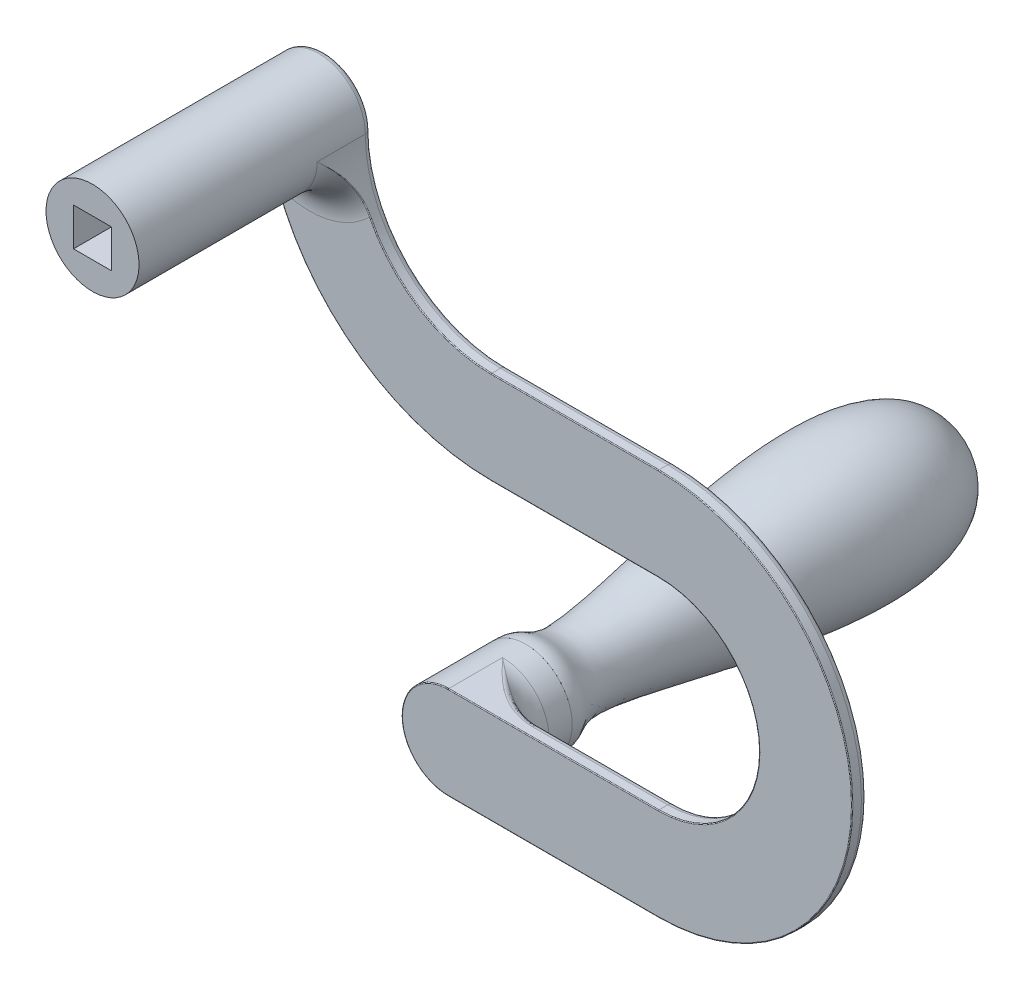
SolidWorks part; units mm, degrees
ref_plane "Front" through (0, 0, 0) normal (0, 0, 1) x (1, 0, 0)
ref_plane "Top" through (0, 0, 0) normal (0, 1, 0) x (1, 0, 0)
ref_plane "Right" through (0, 0, 0) normal (1, 0, 0) x (0, 0, -1)
sketch "Sketch1" plane through (0, 0, 0) normal (0, 0, 1) x (1, 0, 0)
  line L0 (-21.5754, 25) -> (0, 25)
  line L1 (-27.1185, -25) -> (0, -25)
  line L2 (-21.5754, 13) -> (0, 13)
  line L3 (-27.1185, -13) -> (0, -13)
  line L4 (-51.0187, 42.4433) -> (-39.0187, 42.4433)
  line L5 (-27.1185, -13) -> (-27.1185, -25)
  arc A1 (-39.0187, 42.4433) -> (-21.5754, 25) centre (-21.5754, 42.4433) ccw
  arc A2 (0, -25) -> (0, 25) centre (0, 0) ccw
  arc A3 (-51.0187, 42.4433) -> (-21.5754, 13) centre (-21.5754, 42.4433) ccw
  arc A4 (0, -13) -> (0, 13) centre (0, 0) ccw
  dimension "D2" = 13
  dimension "D1" = 12
extrude "Boss-Extrude1" add sketch "Sketch1" along normal blind 2
sketch "Sketch2" plane through (0, 0, 2) normal (0, 0, 1) x (1, 0, 0)
  line L0 (-27.1185, -13) -> (-27.1185, -25) construction
  line L1 (-27.1185, -13) -> (-27.1185, -25) construction
  circle A0 centre (-27.1185, -19) radius 6
  point P4 (-27.1185, -19)
  point P5 (0, 0)
  dimension "D1" = 12
extrude "Boss-Extrude2" add sketch "Sketch2" against normal blind 10
sketch "Sketch3" plane through (0, 0, 0) normal (0, 0, -1) x (-1, 0, 0)
  line L0 (39.0187, 42.4433) -> (51.0187, 42.4433) construction
  circle A0 centre (45.0187, 42.4433) radius 6
  point P4 (45.0187, 42.4433)
  point P5 (0, 0)
  dimension "D1" = 12
extrude "Boss-Extrude3" add sketch "Sketch3" against normal blind 30
sketch "Sketch4" plane through (0, 0, 30) normal (0, 0, 1) x (1, 0, 0)
  line L0 (-45.0187, 42.4433) -> (-51.0187, 42.4433) construction
  line L1 (-45.0187, 42.4433) -> (-45.0187, 36.4433) construction
  line L3 (-47.4687, 39.9933) -> (-42.5687, 39.9933)
  line L4 (-47.4687, 39.9933) -> (-47.4687, 44.8933)
  line L5 (-47.4687, 44.8933) -> (-42.5687, 44.8933)
  line L6 (-42.5687, 39.9933) -> (-42.5687, 44.8933)
  circle A0 centre (-45.0187, 42.4433) radius 6 construction
  point P10 (-47.4687, 42.4433)
  point P11 (-45.0187, 39.9933)
  dimension "D1" = 4.9
  dimension "D2" = 4.9
extrude "Cut-Extrude1" cut sketch "Sketch4" against normal blind 10
fillet "Fillet8" radius 5 1 edges at (-21.1185, -19, 0)
fillet "Fillet9" radius 5 1 edges at (-45.0187, 36.4433, 2)
sketch "Sketch6" plane through (0, 0, -8) normal (0, 0, -1) x (-1, 0, 0)
  circle A0 centre (27.1185, -19) radius 4.5
  dimension "D1" = 9
extrude "Cut-Extrude2" cut sketch "Sketch6" against normal blind 3 contours A0
sketch "Sketch9" plane through (0, 0, -5) normal (0, 0, -1) x (-1, 0, 0)
  circle A1 centre (27.1185, -19) radius 4.5
  circle A2 centre (27.1185, -19) radius 4.5
  dimension "D1" = 0
ref_plane "Plane2" through (0, -19, 0) normal (0, 1, 0) x (1, 0, 0)
sketch "Sketch10" plane through (0, -19, 0) normal (0, 1, 0) x (1, 0, 0)
  line L0 (-27.1185, 5) -> (-27.1185, 37.9838) construction
  line L1 (-27.1185, 5) -> (-31.5837, 5)
  line L2 (-31.5837, 5) -> (-31.5837, 8)
  line L3 (-22.6185, 5) -> (-31.6185, 5) construction
  line L4 (-21.1185, 8) -> (-33.1185, 8) construction
  line L5 (-31.5837, 8) -> (-33.1185, 8)
  line L6 (-27.1185, 5) -> (-27.1185, 62.835)
  spline S0 degree 3 poles (-33.1185, 8) (-33.3312, 10.2616) (-27.1279, 11.4717) (-44.9894, 62.6911) (-27.1185, 62.835) knots 0 0 0 0 0.217637 1 1 1 1
  point P8 (-27.1185, 47.5968)
  point P11 (-32.3962, 10.8585)
  point P14 (-35.5074, 21.2698)
  point P15 (-33.135, 15.5218)
  point P16 (-34.1401, 17.8453)
  point P17 (0, 0)
  point P18 (-32.93, 15.5033)
  point P19 (0, 0)
  point P20 (-27.1185, 62.835)
revolve "Revolve1" add sketch "Sketch10" angle 360 about L0
fillet "Fillet10" radius 0.8 11 edges at (-20.399, -25, -0.4137) (-8.9495, -25, 0) (-20.399, -13, -0.4137) (-8.9495, -13, 0) (13, 0, 0) (-10.7877, 13, 0) (-42.395, 21.6237, 0) (-45.0187, 48.4433, 0) (-33.9097, 30.109, 0) (-10.7877, 25, 0) (25, 0, 0)
fillet "Fillet11" radius 0.1 11 edges at (-50.1436, 35.3184, 2.5215) (-38.419, 18.2937, 2) (-10.7877, 13, 2) (13, 0, 2) (-13.5593, -13, 2) (-33.1185, -19, 2) (-37.9979, 36.5636, 2.3518) (-30.7732, 27.6221, 2) (-10.7877, 25, 2) (25, 0, 2) (-13.5593, -25, 2)
